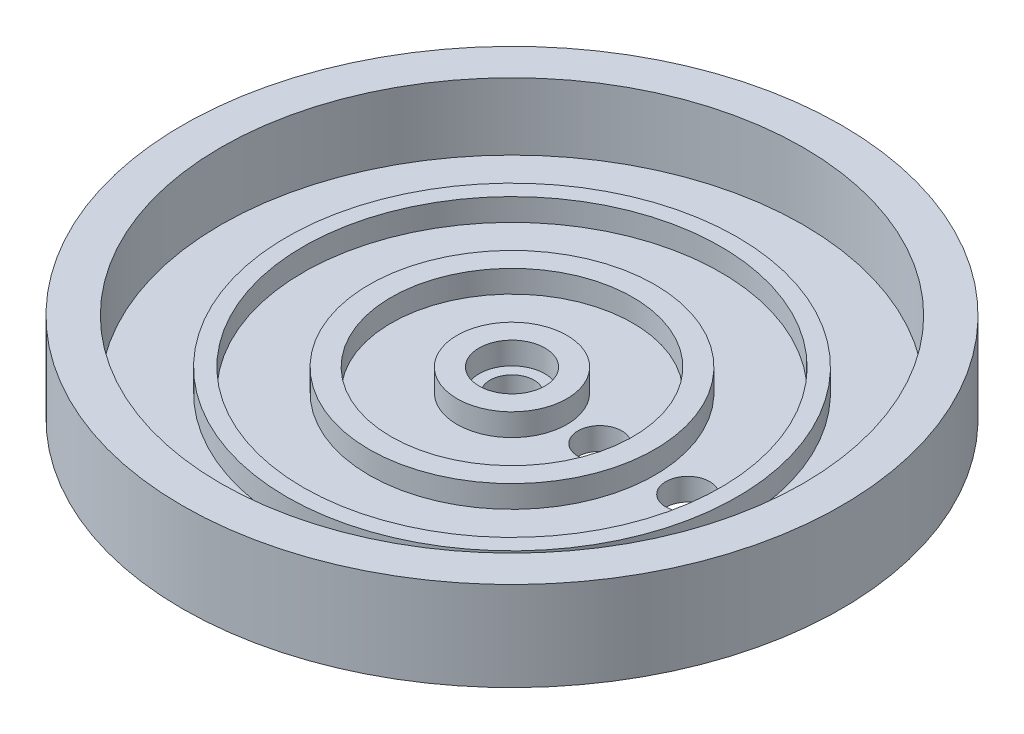
SolidWorks part; units mm, degrees
material "ABS"
ref_plane "Front Plane" through (0, 0, 0) normal (0, 0, 1) x (1, 0, 0)
ref_plane "Top Plane" through (0, 0, 0) normal (0, 1, 0) x (1, 0, 0)
ref_plane "Right Plane" through (0, 0, 0) normal (1, 0, 0) x (0, 0, -1)
sketch "Sketch2" plane through (0, 0, 0) normal (0, 1, 0) x (1, 0, 0)
  circle A0 centre (0, 0) radius 1
  circle A1 centre (4, 0) radius 1
  circle A2 centre (8, 0) radius 1
  circle A4 centre (0, 0) radius 15
  circle A6 centre (0, 0) radius 9 construction
  circle A7 centre (0, 0) radius 11 construction
  point P19 (0, 0)
  dimension "D1" = 2
  dimension "D3" = 30
  dimension "D4" = 2
  dimension "D5" = 4
  dimension "D2" = 3
extrude "Boss-Extrude2" add sketch "Sketch2" along normal blind 1.016
sketch "Sketch3" plane through (0, 1.016, 0) normal (0, 1, 0) x (1, 0, 0)
  circle A2 centre (0, 0) radius 1.5
  circle A4 centre (0, 0) radius 2.5
  circle A5 centre (0, 0) radius 5.5
  circle A6 centre (0, 0) radius 6.5
  circle A7 centre (0, 0) radius 9.5
  circle A11 centre (0, 0) radius 10.25
  circle A13 centre (0, 0) radius 13.25
  circle A14 centre (0, 0) radius 15
  circle M4 centre (0, 0) radius 15
  dimension "D1" = 3
  dimension "D2" = 3
  dimension "D3" = 3
  dimension "D4" = 1
  dimension "D5" = 5
  dimension "D7" = 3
  dimension "D8" = 20.5
extrude "Boss-Extrude4" add sketch "Sketch3" along normal blind 1.016 contours A13 M4 | A11 A7 | A6 A5 | A4 A2 region at (-2.4293, 1.016, 0) region at (-6.3162, 1.016, 0) region at (-9.9601, 1.016, 0) region at (-14.5757, 1.016, 0)
sketch "Sketch5" plane through (0, 2.032, 0) normal (0, 1, 0) x (1, 0, 0)
  circle A0 centre (0, 0) radius 13.25
  circle A1 centre (0, 0) radius 15
extrude "Boss-Extrude5" add sketch "Sketch5" along normal blind 2.032
